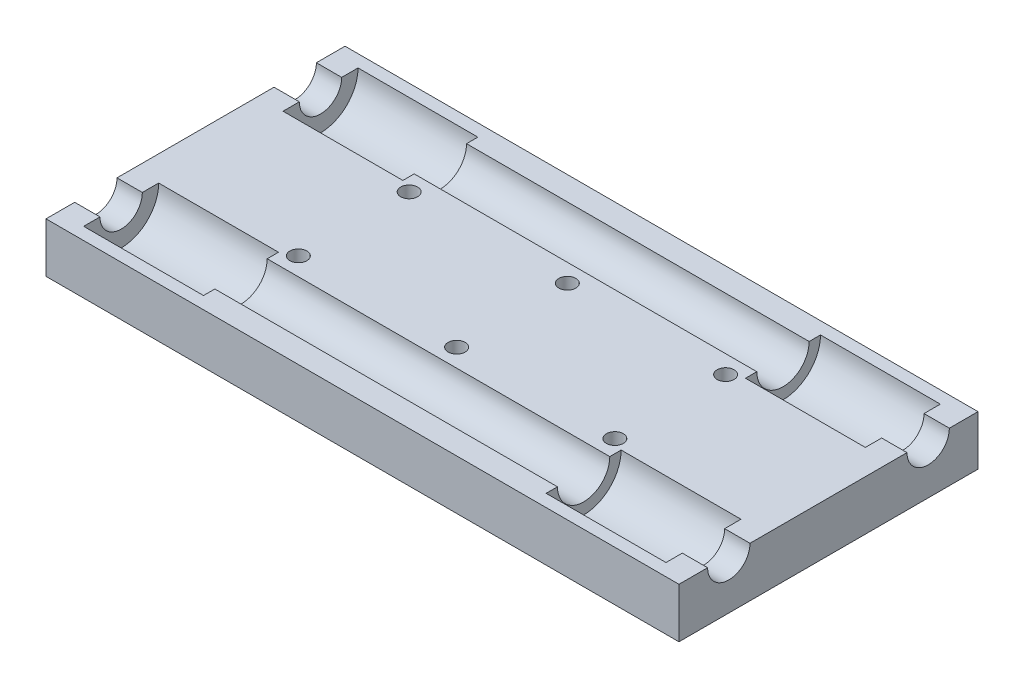
SolidWorks part; units mm, degrees
ref_plane "Front Plane" through (0, 0, 0) normal (0, 0, 1) x (1, 0, 0)
ref_plane "Top Plane" through (0, 0, 0) normal (0, 1, 0) x (1, 0, 0)
ref_plane "Right Plane" through (0, 0, 0) normal (1, 0, 0) x (0, 0, -1)
ref_axis "Axis X" through (-88.99, 0, 0) along (1, 0, 0)
ref_axis "Axis Y" through (0, 55, 0) along (0, -1, 0)
ref_axis "Axis Z" through (0, 0, -88.99) along (0, 0, 1)
sketch "Sketch1" plane through (0, 0, 0) normal (0, 1, 0) x (1, 0, 0)
  line L1 (-63.5, -30) -> (63.5, -30)
  line L2 (-63.5, -30) -> (-63.5, 30)
  line L3 (-63.5, 30) -> (63.5, 30)
  line L4 (63.5, -30) -> (63.5, 30)
  line L5 (-63.5, -30) -> (63.5, 30) construction
  line L6 (-63.5, 30) -> (63.5, -30) construction
  point P0 (0, 0)
  dimension "D1" = 60
  dimension "D2" = 127
extrude "Boss-Extrude1" add sketch "Sketch1" along normal blind 10
sketch "Sketch3" plane through (-63.5, 0, 0) normal (-1, 0, 0) x (0, 0, 1)
  line L0 (0, 0) -> (0, 19.22) construction
  line L1 (0, -5.5) -> (0, 5.5) construction
  line L4 (-30, 10) -> (30, 10) construction
  circle A0 centre (-20, 10) radius 7.525
  circle A1 centre (20, 10) radius 7.525
  dimension "D1" = 15.05
  dimension "D2" = 40
  dimension "D3" = 2.475
extrude "Cut-Extrude1" cut sketch "Sketch3" against normal blind 24.05 from offset 5.08 contours A0 | A1 offset against normal yes
mirror "Mirror1" about plane through (0, 0, 0) normal (1, 0, 0) of "Cut-Extrude1"
sketch "Sketch4" plane through (-58.42, 0, 0) normal (1, 0, 0) x (0, 0, -1)
  circle A0 centre (20, 10) radius 4.25
  arc A1 (12.475, 10) -> (27.525, 10) centre (20, 10) ccw construction
  dimension "D1" = 8.5
extrude "Cut-Extrude2" cut sketch "Sketch4" against normal up to next and the other way up to surface other way up to face at (63.5, 5, 0)
mirror "Mirror2" about plane through (0, 0, 0) normal (0, 0, 1) of "Cut-Extrude2"
sketch "Sketch5" plane through (34.37, 0, 0) normal (1, 0, 0) x (0, 0, -1)
  arc A0 (-24.25, 10) -> (-15.75, 10) centre (-20, 10) ccw construction
  circle A1 centre (-20, 10) radius 4.25
  circle A2 centre (-20, 10) radius 5.25
  dimension "D1" = 1
extrude "Cut-Extrude3" cut sketch "Sketch5" against normal up to surface (68.74 mm away) up to face at (-34.37, 7.0563, 20)
mirror "Mirror3" about plane through (0, 0, 0) normal (0, 0, 1) of "Cut-Extrude3"
hole_wizard "CBORE for M3 SHCS1" positions "Sketch7" profile "Sketch6" counterbore size "M3" standard "ANSI Metric" end condition through all
sketch "Sketch7" plane through (0, 0, 0) normal (0, -1, 0) x (-1, 0, 0)
  line L0 (0, 0) -> (98.4212, 0) construction
  line L1 (-5.5, 0) -> (5.5, 0) construction
  line L3 (0, 0) -> (0, 49.0836) construction
  line L5 (0, 5.5) -> (0, -5.5) construction
  point P0 (-31.75, -11.1125)
  point P2 (0, -11.1125)
  point P4 (31.75, -11.1125)
  point P6 (-31.75, 11.1125)
  point P8 (0, 11.1125)
  point P10 (31.75, 11.1125)
  dimension "D1" = 22.225
  dimension "D2" = 31.75
sketch "Sketch6" plane through (31.75, 0, 11.1125) normal (1, 0, 0) x (0, 0, -1)
  line L0 (0, 0) -> (0, 10)
  line L1 (0, 10) -> (1.7, 10)
  line L3 (1.7, 10) -> (1.7, 3.254)
  line L4 (1.7, 3.254) -> (3.25, 3.254)
  line L5 (3.25, 3.254) -> (3.25, 0)
  line L7 (3.25, 0) -> (0, 0)
  line L11 (0, -6.35) -> (0, 107.95) construction
  dimension "Thru Hole Dia." = 3.4
  dimension "Thru Hole Depth" = 10
  dimension "C'Bore Dia." = 6.5
  dimension "C'Bore Depth" = 3.254
